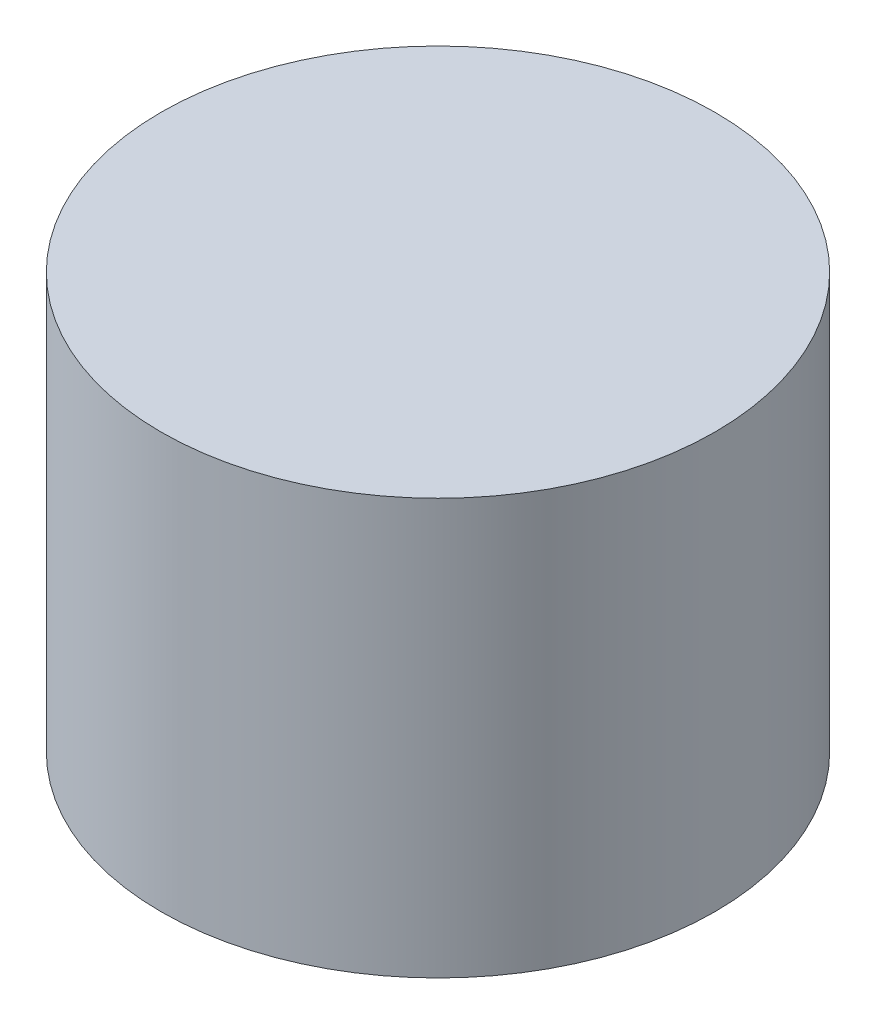
SolidWorks part; units mm, degrees
ref_plane "Front Plane" through (0, 0, 0) normal (0, 0, 1) x (1, 0, 0)
ref_plane "Top Plane" through (0, 0, 0) normal (0, 1, 0) x (1, 0, 0)
ref_plane "Right Plane" through (0, 0, 0) normal (1, 0, 0) x (0, 0, -1)
sketch "Sketch1" plane through (0, 0, 0) normal (0, 1, 0) x (1, 0, 0)
  circle A0 centre (0, 0) radius 6.35
  dimension "D1" = 12.7
extrude "Boss-Extrude1" add sketch "Sketch1" along normal blind 9.525
equation "\"R\"= 1.5in'radius of rotor"
equation "\"E\"= .125in'eccentricity"
equation "\"R_r\"= .25in'radius of roller"
equation "\"N\"= 8'number of rollers"
equation "\"R_o\"= .125in'output disk pin diameter"
equation "\"D1@Sketch1\"=2*\"R_r\""
